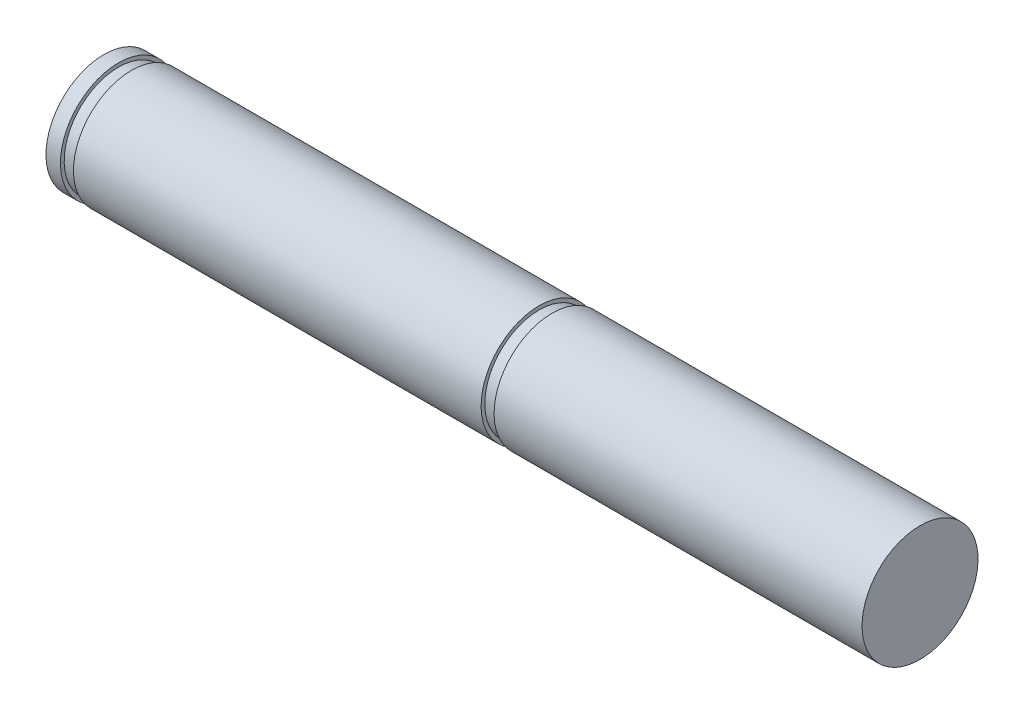
SolidWorks part; units mm, degrees
ref_plane "Front Plane" through (0, 0, 0) normal (0, 0, 1) x (1, 0, 0)
ref_plane "Top Plane" through (0, 0, 0) normal (0, 1, 0) x (1, 0, 0)
ref_plane "Right Plane" through (0, 0, 0) normal (1, 0, 0) x (0, 0, -1)
sketch "Sketch1" plane through (0, 0, 0) normal (0, 0, 1) x (1, 0, 0)
  line L0 (0, 0) -> (0, 6.35)
  line L1 (0, 6.35) -> (1.5875, 6.35)
  line L4 (89.3699, 6.35) -> (89.3699, 0)
  line L5 (89.3699, 0) -> (0, 0)
  line L6 (1.5875, 6.35) -> (1.5875, 5.9436)
  line L7 (1.5875, 5.9436) -> (3.0099, 5.9436)
  line L8 (3.0099, 5.9436) -> (3.0099, 6.35)
  line L9 (3.0099, 6.35) -> (47.6504, 6.35)
  line L10 (0, 0) -> (-5.7237, 0) construction
  line L11 (47.6504, 6.35) -> (47.6504, 5.9436)
  line L12 (47.6504, 5.9436) -> (49.0728, 5.9436)
  line L13 (49.0728, 5.9436) -> (49.0728, 6.35)
  line L14 (49.0728, 6.35) -> (89.3699, 6.35)
  dimension "D4" = 1.5875
  dimension "D7" = 1.4224
  dimension "D9" = 1.4224
  dimension "D10" = 11.8872
  dimension "D2" = 86.36
  dimension "D3" = 44.6405
  dimension "D5" = 12.7
revolve "Revolve1" add sketch "Sketch1" angle 360 about L10
equation "\"D7@Sketch1\"=\"D9@Sketch1\""
